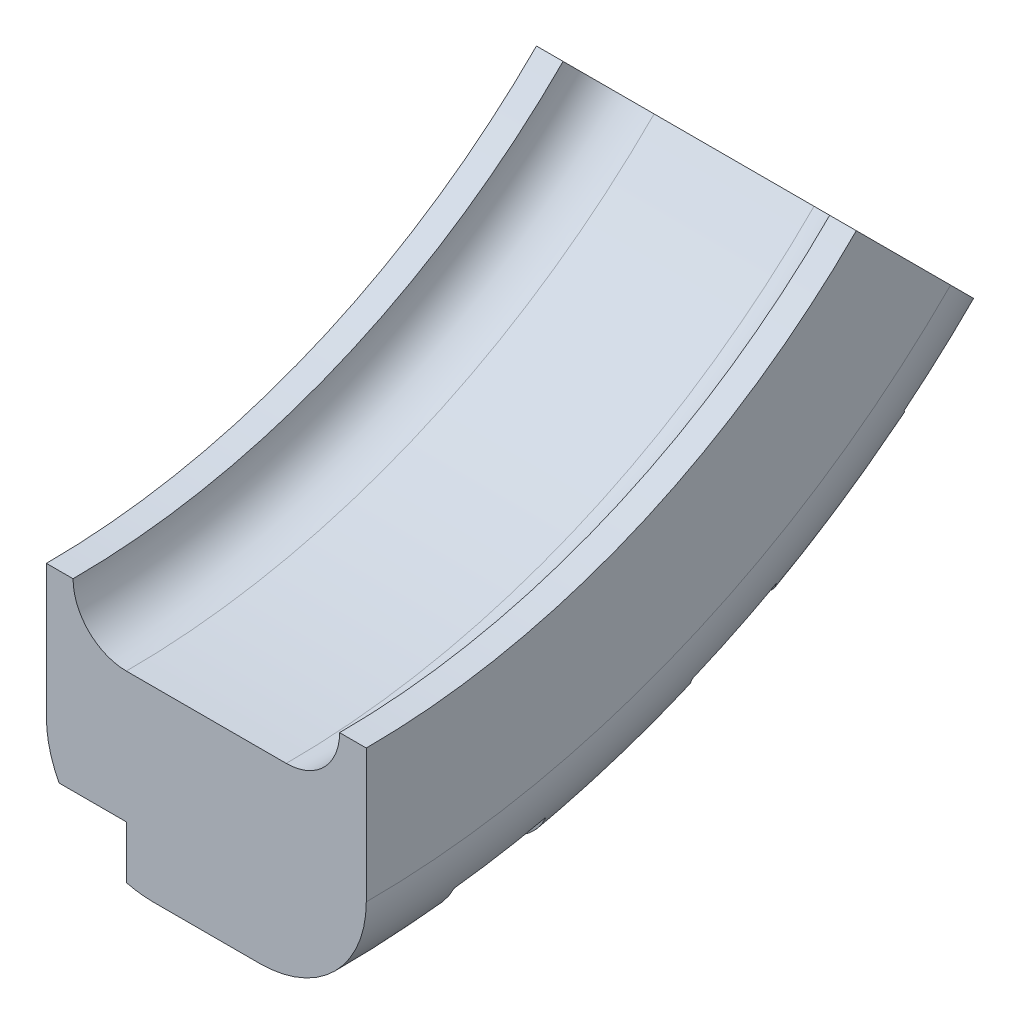
SolidWorks part; units mm, degrees
ref_plane "Front" through (0, 0, 0) normal (0, 0, 1) x (1, 0, 0)
ref_plane "Top" through (0, 0, 0) normal (0, 1, 0) x (1, 0, 0)
ref_plane "Right" through (0, 0, 0) normal (1, 0, 0) x (0, 0, -1)
sketch "Sketch1" plane through (0, 0, 0) normal (0, 0, 1) x (1, 0, 0)
  line L0 (0.3529, 0) -> (29561.5174, 0) construction
  line L1 (-5, -28) -> (5, -28)
  line L2 (5, -28) -> (5, -26)
  line L3 (5, -26) -> (6, -26)
  line L4 (6, -26) -> (6, -35) construction
  line L5 (6, -35) -> (-6, -35) construction
  line L6 (-6, -35) -> (-6, -26) construction
  line L7 (-6, -26) -> (-5, -26)
  line L8 (-5, -26) -> (-5, -28)
  line L9 (2, -35) -> (-2, -35)
  line L10 (6, -31) -> (6, -26)
  line L11 (-6, -26) -> (-6, -31)
  arc A0 (-2, -35) -> (-6, -31) centre (-2, -31) cw
  arc A1 (2, -35) -> (6, -31) centre (2, -31) ccw
  point P5 (0, -28)
  point P12 (0, -35)
  dimension "D6" = 4
  dimension "D1" = 12
  dimension "D2" = 1
  dimension "D3" = 35
  dimension "D4" = 28
  dimension "D5" = 2
revolve "Revolve1" add sketch "Sketch1" angle 45 about L0
sketch "Sketch2" plane through (6, 0, 0) normal (1, 0, 0) x (0, 0, -1)
  line L0 (0, 0) -> (24.7487, -24.7487) construction
  line L1 (21.9796, -27.2378) -> (20.6608, -25.6035)
  line L2 (23.2638, -23.2638) -> (24.7487, -24.7487)
  line L3 (15.8724, -28.818) -> (16.8856, -30.6574)
  line L4 (13.5332, -32.2777) -> (12.7212, -30.3411)
  line L5 (7.2276, -32.0963) -> (7.6889, -34.145)
  line L6 (4.0181, -34.7686) -> (3.777, -32.6825)
  line L9 (-1.9881, -32.8399) -> (-2.115, -34.936) [skipped]
  line L10 (-5.8144, -34.5137) -> (-5.4655, -32.4428) [skipped]
  arc A0 (24.7487, -24.7487) -> (21.9796, -27.2378) centre (0, 0) cw
  arc A1 (0, -35) -> (24.7487, -24.7487) centre (0, 0) ccw construction
  arc A2 (23.2638, -23.2638) -> (20.6608, -25.6035) centre (0, 0) cw
  arc A3 (16.8856, -30.6574) -> (13.5332, -32.2777) centre (0, 0) cw
  arc A4 (15.8724, -28.818) -> (12.7212, -30.3411) centre (0, 0) cw
  arc A5 (7.6889, -34.145) -> (4.0181, -34.7686) centre (0, 0) cw
  arc A6 (7.2276, -32.0963) -> (3.777, -32.6825) centre (0, 0) cw
  arc A9 (-2.115, -34.936) -> (-5.8144, -34.5137) centre (0, 0) cw [skipped]
  arc A10 (-1.9881, -32.8399) -> (-5.4655, -32.4428) centre (0, 0) cw [skipped]
  point P0 (24.7487, -24.7487)
  point P1 (0, 0)
  point P6 (23.2638, -23.2638)
  dimension "D1" = 2.1
  dimension "D2" = 3.5
  dimension "D3" = 4
extrude "Cut-Extrude1" cut sketch "Sketch2" against normal blind 3
sketch "Sketch3" plane through (-6, 0, 0) normal (-1, 0, 0) x (0, 0, 1)
  line L0 (0, -35) -> (0, -32.9)
  line L1 (0, -26) -> (0, -31) construction
  line L2 (-3.7234, -34.8014) -> (-3.5, -32.7133)
  line L3 (-12.6361, -32.6394) -> (-11.8779, -30.681)
  line L4 (-9.0921, -33.7984) -> (-8.5466, -31.7705)
  line L5 (-20.6812, -28.2363) -> (-19.4403, -26.5421)
  line L6 (-17.5599, -30.2762) -> (-16.5063, -28.4596)
  line L9 (-27.3062, -21.8945) -> (-25.6679, -20.5808) [skipped]
  line L10 (-24.8221, -24.6752) -> (-23.3327, -23.1947) [skipped]
  line L11 (0, -35) -> (0, -31) construction
  arc A0 (0, -35) -> (-3.7234, -34.8014) centre (0, 0) cw
  arc A2 (0, -32.9) -> (-3.5, -32.7133) centre (0, 0) cw
  arc A3 (-18.3848, -18.3848) -> (0, -26) centre (0, 0) ccw construction
  arc A4 (-8.5466, -31.7705) -> (-11.8779, -30.681) centre (0, 0) cw
  arc A5 (-9.0921, -33.7984) -> (-12.6361, -32.6394) centre (0, 0) cw
  arc A6 (-16.5063, -28.4596) -> (-19.4403, -26.5421) centre (0, 0) cw
  arc A7 (-17.5599, -30.2762) -> (-20.6812, -28.2363) centre (0, 0) cw
  arc A10 (-23.3327, -23.1947) -> (-25.6679, -20.5808) centre (0, 0) cw [skipped]
  arc A11 (-24.8221, -24.6752) -> (-27.3062, -21.8945) centre (0, 0) cw [skipped]
  arc A12 (-24.7487, -24.7487) -> (0, -35) centre (0, 0) ccw construction
  dimension "D1" = 2.1
  dimension "D2" = 3.5
  dimension "D3" = 4
extrude "Cut-Extrude2" cut sketch "Sketch3" against normal blind 3
fillet "Fillet1" radius 2 2 edges at (5, -25.8686, -10.7151) (-5, -25.8686, -10.7151)
